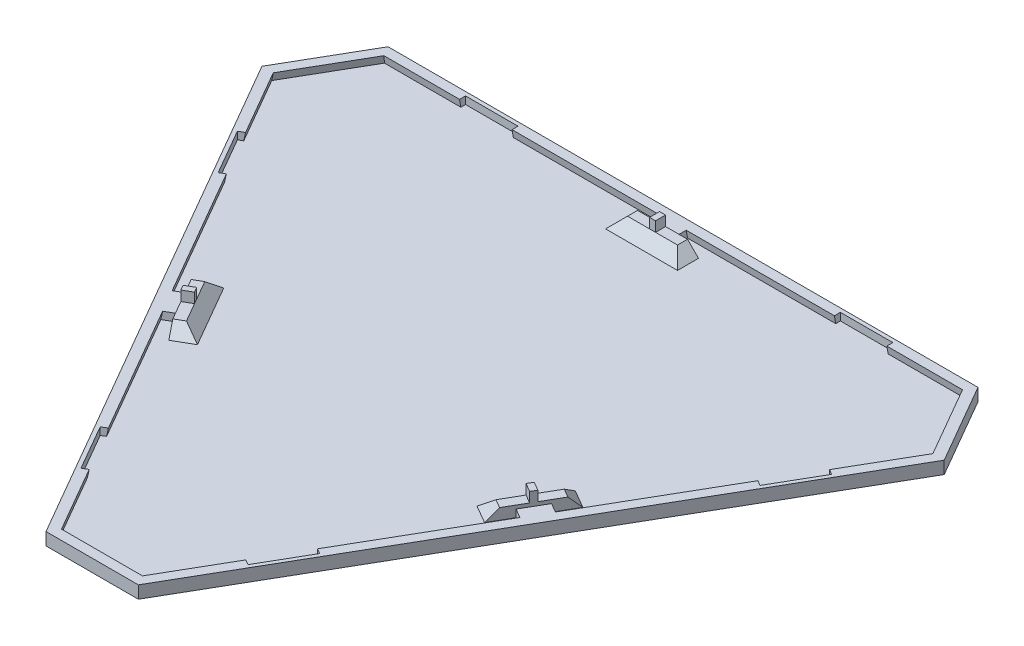
SolidWorks part; units mm, degrees
ref_plane "Plan de face" through (0, 0, 0) normal (0, 0, 1) x (1, 0, 0)
ref_plane "Plan de dessus" through (0, 0, 0) normal (0, 1, 0) x (1, 0, 0)
ref_plane "Plan de droite" through (0, 0, 0) normal (1, 0, 0) x (0, 0, -1)
sketch "Esquisse2" plane through (0, 0, 0) normal (0, 1, 0) x (1, 0, 0)
  line L3 (-59.0248, 44.7446) -> (-68.2624, 28.7446) construction
  line L4 (-59.0248, 44.7446) -> (59.0248, 44.7446) construction
  line L5 (68.2624, 28.7446) -> (9.2376, -73.4893) construction
  line L6 (-68.2624, 28.7446) -> (-59.0248, 44.7446)
  line L7 (59.0248, 44.7446) -> (68.2624, 28.7446)
  line L8 (9.2376, -73.4893) -> (-9.2376, -73.4893)
  line L9 (-68.2624, 28.7446) -> (-9.2376, -73.4893)
  line L10 (9.2376, -73.4893) -> (68.2624, 28.7446)
  line L11 (59.0248, 44.7446) -> (-59.0248, 44.7446)
  line L12 (-9.2376, -73.4893) -> (-68.2624, 28.7446) construction
  line L13 (-9.2376, -73.4893) -> (9.2376, -73.4893) construction
  line L14 (68.2624, 28.7446) -> (59.0248, 44.7446) construction
  point P16 (0, 0)
extrude "Boss.-Extru.2" add sketch "Esquisse2" along normal blind 1
sketch "Esquisse5" plane through (0, 1, 0) normal (0, 1, 0) x (1, 0, 0)
  line L19 (-68.2624, 28.7446) -> (-9.2376, -73.4893)
  line L20 (-9.2376, -73.4893) -> (9.2376, -73.4893)
  line L21 (9.2376, -73.4893) -> (68.2624, 28.7446)
  line L26 (68.2624, 28.7446) -> (59.0248, 44.7446)
  line L27 (59.0248, 44.7446) -> (-59.0248, 44.7446)
  line L32 (-59.0248, 44.7446) -> (-68.2624, 28.7446)
  line L37 (-68.2624, 28.7446) -> (-9.2376, -73.4893)
  line L38 (-9.2376, -73.4893) -> (9.2376, -73.4893)
  line L39 (9.2376, -73.4893) -> (68.2624, 28.7446)
  line L44 (68.2624, 28.7446) -> (59.0248, 44.7446)
  line L45 (59.0248, 44.7446) -> (-59.0248, 44.7446)
  line L50 (-59.0248, 44.7446) -> (-68.2624, 28.7446)
  dimension "D1" = 0
extrude "Extru.-Mince1" add sketch "Esquisse5" along normal blind 1.5 draft 10 thin draft outward yes thin type one direction reverse wall 1.7
sketch "Esquisse6" plane through (0, 0, 0) normal (0, -1, 0) x (1, 0, 0)
  line L6 (-59.0248, -44.7446) -> (59.0248, -44.7446)
  line L7 (59.0248, -44.7446) -> (68.2624, -28.7446)
  line L8 (68.2624, -28.7446) -> (9.2376, 73.4893)
  line L9 (9.2376, 73.4893) -> (-9.2376, 73.4893)
  line L10 (-9.2376, 73.4893) -> (-68.2624, -28.7446)
  line L11 (-68.2624, -28.7446) -> (-59.0248, -44.7446)
  line L12 (-59.0248, -44.7446) -> (59.0248, -44.7446)
  line L13 (59.0248, -44.7446) -> (68.2624, -28.7446)
  line L14 (68.2624, -28.7446) -> (9.2376, 73.4893)
  line L15 (9.2376, 73.4893) -> (-9.2376, 73.4893)
  line L16 (-9.2376, 73.4893) -> (-68.2624, -28.7446)
  line L17 (-68.2624, -28.7446) -> (-59.0248, -44.7446)
  dimension "D1" = 0
extrude "Enlèv. de mat.-Extru.-Mince1" cut sketch "Esquisse6" against normal through all thin thin type one direction wall 1.5
sketch "Esquisse7" plane through (0, 1, 0) normal (0, 1, 0) x (1, 0, 0)
  line L0 (2.6, 44.7446) -> (-2.6, 44.7446)
  line L1 (2.6, 44.7446) -> (2.6, 40.6446)
  line L2 (-2.6, 44.7446) -> (-2.6, 40.6446)
  line L3 (2.6, 40.6446) -> (-2.6, 40.6446)
  line L4 (-59.0248, 44.7446) -> (59.0248, 44.7446) construction
  line L5 (33.8993, -22.574) -> (36.4993, -18.0707)
  line L6 (37.45, -24.624) -> (33.8993, -22.574)
  line L7 (37.45, -24.624) -> (40.05, -20.1207)
  line L8 (40.05, -20.1207) -> (36.4993, -18.0707)
  line L9 (-36.4993, -18.0707) -> (-33.8993, -22.574)
  line L10 (-40.05, -20.1207) -> (-36.4993, -18.0707)
  line L11 (-40.05, -20.1207) -> (-37.45, -24.624)
  line L12 (-37.45, -24.624) -> (-33.8993, -22.574)
  point P6 (0, 44.7446)
  point P7 (0, 44.7446)
  point P19 (0, 0)
  dimension "D1" = 4.1
  dimension "D2" = 5.2
  dimension "D3" = 3
extrude "Boss.-Extru.5" add sketch "Esquisse7" along normal up to surface (1.5 mm away) up to face at (0, 2.5, 0)
sketch "Esquisse8" plane through (0, 1, 0) normal (0, 1, 0) x (1, 0, 0)
  line L0 (-2.6, 40.6446) -> (2.6, 40.6446) construction
  line L1 (-5, 40.6446) -> (5, 40.6446)
  line L2 (-5, 40.6446) -> (-5, 38.6446)
  line L3 (-5, 38.6446) -> (5, 38.6446)
  line L4 (5, 40.6446) -> (5, 38.6446)
  line L5 (37.6993, -15.9922) -> (32.6993, -24.6524)
  line L6 (37.6993, -15.9922) -> (35.9672, -14.9922)
  line L7 (35.9672, -14.9922) -> (30.9672, -23.6524)
  line L8 (32.6993, -24.6524) -> (30.9672, -23.6524)
  line L9 (-32.6993, -24.6524) -> (-37.6993, -15.9922)
  line L10 (-32.6993, -24.6524) -> (-30.9672, -23.6524)
  line L11 (-30.9672, -23.6524) -> (-35.9672, -14.9922)
  line L12 (-37.6993, -15.9922) -> (-35.9672, -14.9922)
  point P7 (0, 40.6446)
  point P8 (0, 40.6446)
  point P18 (0, 0)
  dimension "D1" = 10
  dimension "D2" = 2
  dimension "D3" = 3
extrude "Boss.-Extru.6" add sketch "Esquisse8" along normal blind 2.2
chamfer "Chanfrein1" distance 2.2 angle 45 9 edges at (-31.8333, 1, 24.1524) (-36.8333, 1, 15.4922) (-33.4672, 1, 19.3223) (36.8333, 1, 15.4922) (33.4672, 1, 19.3223) (31.8333, 1, 24.1524) (5, 1, -39.6446) (-5, 1, -39.6446) (0, 1, -38.6446)
sketch "Esquisse9" plane through (0, 3.2, 0) normal (0, 1, 0) x (1, 0, 0)
  line L0 (5, 40.6446) -> (-5, 40.6446) construction
  line L1 (0.6, 40.6446) -> (-0.6, 40.6446)
  line L2 (0.6, 40.6446) -> (0.6, 38.6446)
  line L3 (0.6, 38.6446) -> (-0.6, 38.6446)
  line L4 (-0.6, 40.6446) -> (-0.6, 38.6446)
  line L5 (-5, 38.6446) -> (5, 38.6446) construction
  line L6 (34.8993, -20.8419) -> (35.4993, -19.8027)
  line L7 (34.8993, -20.8419) -> (33.1672, -19.8419)
  line L8 (33.1672, -19.8419) -> (33.7672, -18.8027)
  line L9 (35.4993, -19.8027) -> (33.7672, -18.8027)
  line L10 (-35.4993, -19.8027) -> (-34.8993, -20.8419)
  line L11 (-35.4993, -19.8027) -> (-33.7672, -18.8027)
  line L12 (-33.7672, -18.8027) -> (-33.1672, -19.8419)
  line L13 (-34.8993, -20.8419) -> (-33.1672, -19.8419)
  point P6 (0, 40.6446)
  point P7 (0, 40.6446)
  point P21 (0, 0)
  dimension "D1" = 1.2
  dimension "D2" = 3
extrude "Boss.-Extru.7" add sketch "Esquisse9" along normal blind 2
sketch "Esquisse10" plane through (0, 2.5, 0) normal (0, 1, 0) x (1, 0, 0)
  line L0 (0, 44.7446) -> (0, 32.7785) construction
  line L1 (-32.25, 43.9802) -> (-42.75, 43.9802)
  line L2 (-32.25, 43.9802) -> (-32.25, 39.7025)
  line L3 (-32.25, 39.7025) -> (-42.75, 39.7025)
  line L4 (-42.75, 43.9802) -> (-42.75, 39.7025)
  line L5 (-2.6, 42.7802) -> (-57.8906, 42.7802) construction
  line L7 (-59.0248, 44.7446) -> (59.0248, 44.7446) construction
  line L8 (42.75, 43.9802) -> (42.75, 39.7025)
  line L9 (32.25, 39.7025) -> (42.75, 39.7025)
  line L10 (32.25, 43.9802) -> (32.25, 39.7025)
  line L11 (32.25, 43.9802) -> (42.75, 43.9802)
  line L12 (54.2129, 5.9392) -> (59.4629, 15.0325)
  line L13 (54.2129, 5.9392) -> (50.5084, 8.0781)
  line L14 (50.5084, 8.0781) -> (55.7584, 17.1713)
  line L15 (59.4629, 15.0325) -> (55.7584, 17.1713)
  line L16 (16.7129, -59.0127) -> (13.0084, -56.8738)
  line L17 (18.2584, -47.7806) -> (13.0084, -56.8738)
  line L18 (21.9629, -49.9194) -> (18.2584, -47.7806)
  line L19 (21.9629, -49.9194) -> (16.7129, -59.0127)
  line L20 (-21.9629, -49.9194) -> (-16.7129, -59.0127)
  line L21 (-21.9629, -49.9194) -> (-18.2584, -47.7806)
  line L22 (-18.2584, -47.7806) -> (-13.0084, -56.8738)
  line L23 (-16.7129, -59.0127) -> (-13.0084, -56.8738)
  line L24 (-59.4629, 15.0325) -> (-55.7584, 17.1713)
  line L25 (-50.5084, 8.0781) -> (-55.7584, 17.1713)
  line L26 (-54.2129, 5.9392) -> (-50.5084, 8.0781)
  line L27 (-54.2129, 5.9392) -> (-59.4629, 15.0325)
  point P11 (-37.5, 43.9802)
  point P16 (-9.2847, 2.5365)
  point P35 (0, 0)
  dimension "D1" = 1.2
  dimension "D2" = 10.5
  dimension "D3" = 75
  dimension "D4" = 3
extrude "Enlèv. mat.-Extru.1" cut sketch "Esquisse10" against normal up to surface (1.5 mm away) up to face at (0, 1, 0)
